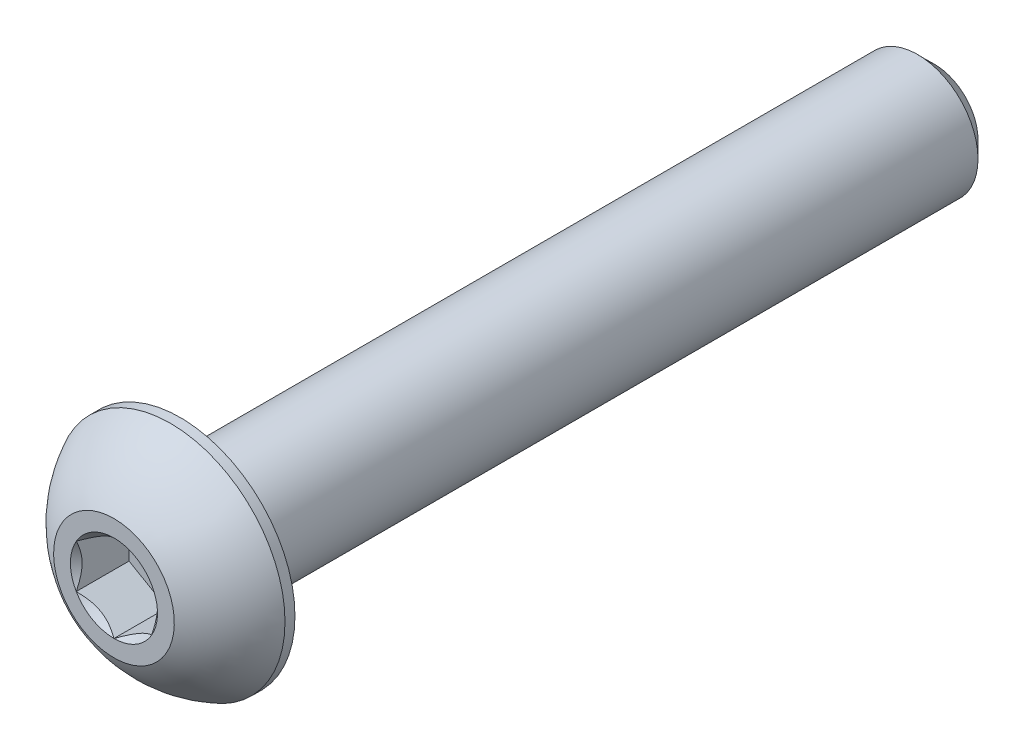
SolidWorks part; units mm, degrees
ref_plane "Front Plane" through (0, 0, 0) normal (0, 0, 1) x (1, 0, 0)
ref_plane "Top Plane" through (0, 0, 0) normal (0, 1, 0) x (1, 0, 0)
ref_plane "Right Plane" through (0, 0, 0) normal (1, 0, 0) x (0, 0, -1)
sketch "Sketch1" plane through (0, 0, 0) normal (1, 0, 0) x (0, 0, -1)
  line L0 (-13.6, 0) -> (13.6, 0) construction
  line L1 (-11.4, 3.8) -> (-11.4, -3.8) construction
  line L2 (13.6, 2) -> (13.6, -2) construction
  line L3 (13.5563, 2.0758) -> (13.9063, 1.4696) construction
  line L4 (13.9063, 1.4696) -> (14.2563, 2.0758) construction
  line L5 (14.2563, 2.0758) -> (13.5563, 2.0758) construction
  line L6 (13.6, 2) -> (14.2125, 2) construction
  line L7 (13.9063, 2.0758) -> (13.9063, 2) construction
  line L8 (13.9063, 2) -> (13.9063, 1.5453) construction
  line L9 (13.9063, 1.5453) -> (13.9063, 1.4696) construction
  line L10 (13.8625, 1.5453) -> (13.95, 1.5453)
  line L11 (13.5781, 2.0379) -> (14.2344, 2.0379)
  line L12 (13.95, 1.5453) -> (14.2344, 2.0379)
  line L13 (13.8625, 1.5453) -> (13.5781, 2.0379)
  line L14 (-13.6, 1.25) -> (-13.6, -1.25) construction
  line L15 (13.6, 2) -> (-11.4, 2) construction
  point P3 (-11.4, 0)
  point P6 (-11.85, 0)
  point P21 (13.9063, 2.0379)
  point P24 (-11.73, 3.8)
  point P25 (11.85, -2)
  point P26 (-13.6, 2)
  dimension "Head Height" = 2.2
  dimension "Length" = 25
  dimension "Head Dia" = 7.6
  dimension "Thread Dia" = 4
  dimension "Pitch" = 0.7
  dimension "D2" = 0.0875
  dimension "Drive Size" = 2.5
  dimension "D1" = 1.75
  dimension "D3" = 0.33
  dimension "D4" = 1.75
sketch "Sketch2" plane through (0, 0, 0) normal (1, 0, 0) x (0, 0, -1)
  line L0 (-13.6, 0) -> (13.6, 0)
  line L1 (13.6, 0) -> (13.6, 1.44)
  line L2 (13.6, 2) -> (13.6, -2) construction
  line L3 (13.6, 1.44) -> (13.04, 2)
  line L4 (13.04, 2) -> (-11.4, 2)
  line L5 (-11.4, 3.8) -> (-11.4, -3.8) construction
  line L6 (-11.4, 2) -> (-11.4, 3.8)
  line L7 (-11.4, 3.8) -> (-11.73, 3.8)
  line L8 (13.6, 2) -> (14.2125, 2) construction
  line L9 (-13.6, 0) -> (-13.6, 2)
  arc A0 (-13.6, 2) -> (-11.73, 3.8) centre (-9.8736, 0) cw
  dimension "D1" = 0.56
  dimension "D2" = 45
revolve "Revolve1" add sketch "Sketch2" angle 360 about L0
sketch "Sketch3" plane through (0, 0, 13.6) normal (0, 0, 1) x (1, 0, 0)
  line L1 (0, 1.4434) -> (-1.25, 0.7217)
  line L2 (-1.25, 0.7217) -> (-1.25, -0.7217)
  line L3 (-1.25, -0.7217) -> (0, -1.4434)
  line L4 (0, -1.4434) -> (1.25, -0.7217)
  line L5 (1.25, -0.7217) -> (1.25, 0.7217)
  line L6 (1.25, 0.7217) -> (0, 1.4434)
  circle A0 centre (0, 0) radius 1.25 construction
  dimension "D1" = 2.5
extrude "Cut-Extrude1" cut sketch "Sketch3" against normal up to vertex (1.75 mm away) up to point (0, 0, 11.85)
sketch "Sketch4" plane through (0, 0, 13.6) normal (0, 0, 1) x (1, 0, 0)
  circle A0 centre (0, 0) radius 1.4434
extrude "Cut-Extrude2" cut sketch "Sketch4" against normal blind 10 draft 45
split "Split1" [suppressed] bodies to split 106
sketch "Sketch5" [suppressed] plane through (0, 0, -13.6) normal (0, 0, -1) x (-1, 0, 0)
  circle A0 centre (0, 0) radius 2 construction
  circle A1 centre (0, 0) radius 2
curve "Helix/Spiral1" [suppressed] pitch 0.7 height 25.7 turns 36.7143
sketch "Sketch6" [suppressed] plane through (0, 0, 0) normal (1, 0, 0) x (0, 0, -1)
  line L0 (13.8625, 1.5453) -> (13.95, 1.5453) construction
  line L1 (13.8625, 1.5453) -> (13.5781, 2.0379) construction
  line L2 (13.5781, 2.0379) -> (14.2344, 2.0379) construction
  line L3 (13.95, 1.5453) -> (14.2344, 2.0379) construction
  line L4 (13.8625, 1.5453) -> (13.95, 1.5453)
  line L5 (13.8625, 1.5453) -> (13.5781, 2.0379)
  line L6 (13.5781, 2.0379) -> (14.2344, 2.0379)
  line L7 (13.95, 1.5453) -> (14.2344, 2.0379)
sweep "Cut-Sweep1" [suppressed] cut profiles "Sketch6" path "Helix/Spiral1"
sketch "Sketch7" [suppressed] plane through (0, 0, 11.4) normal (0, 0, -1) x (-1, 0, 0)
  circle A1 centre (0, 0) radius 2
  circle A2 centre (0, 0) radius 2
  dimension "D1" = 0
extrude "Boss-Extrude1" [suppressed] add sketch "Sketch7" along normal blind 10 draft 30
equation "\"D2@Sketch1\" = \"Pitch@Sketch1\" / 8"
equation "\"D1@Sketch1\"=\"Drive Size@Sketch1\"*.7"
equation "\"D3@Sketch1\"=\"Head Height@Sketch1\"*.15"
equation "\"D1@Sketch2\"=\"Pitch@Sketch1\"*.8"
equation "\"D1@Sketch3\"=\"Drive Size@Sketch1\""
equation "\"D4@Helix/Spiral1\"=\"Pitch@Sketch1\""
equation "\"D3@Helix/Spiral1\"=\"Length@Sketch1\"+\"Pitch@Sketch1\""
equation "\"D4@Sketch1\"=\"Pitch@Sketch1\"*2.5"
